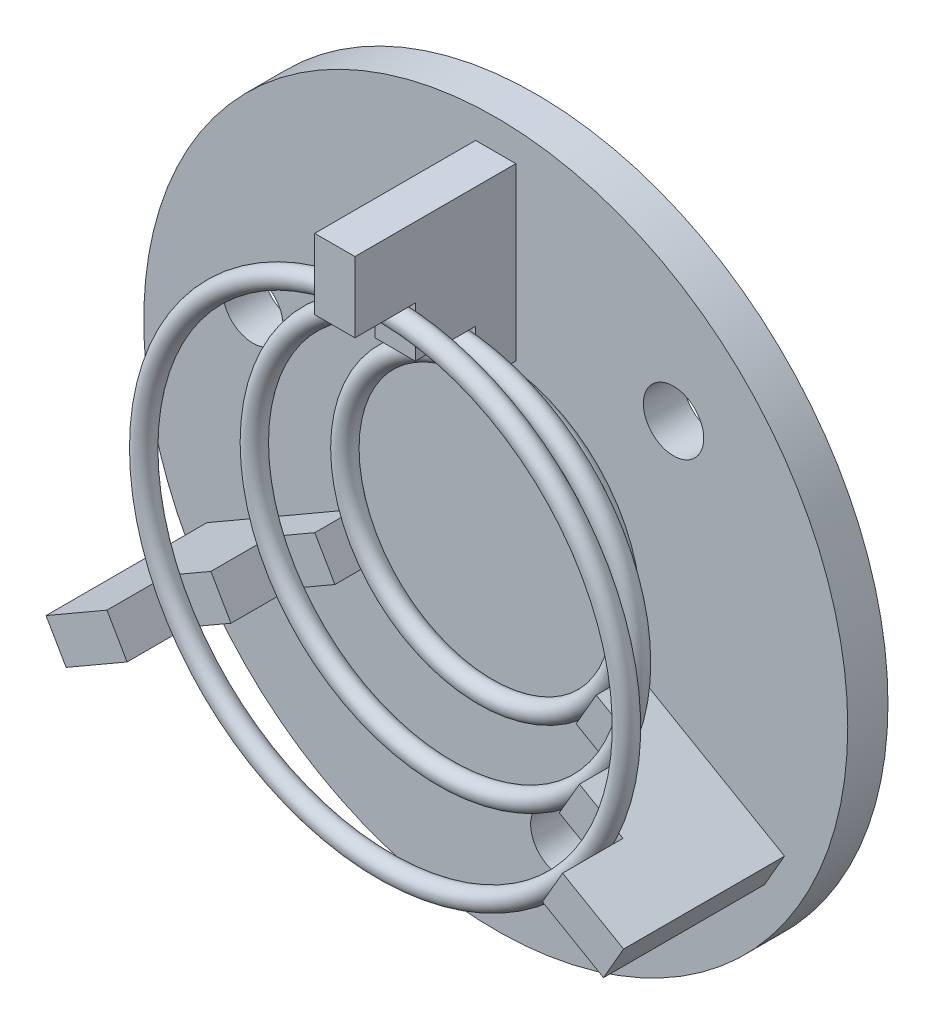
SolidWorks part; units mm, degrees
ref_plane "前视基准面" through (0, 0, 0) normal (0, 0, 1) x (1, 0, 0)
ref_plane "上视基准面" through (0, 0, 0) normal (0, 1, 0) x (1, 0, 0)
ref_plane "右视基准面" through (0, 0, 0) normal (1, 0, 0) x (0, 0, -1)
sketch "草图1" plane through (0, 0, 0) normal (0, 0, 1) x (1, 0, 0)
  circle A0 centre (0, 0) radius 17.5
  dimension "D1" = 35
extrude "凸台-拉伸1" add sketch "草图1" along normal blind 2
sketch "草图2" plane through (0, 0, 0) normal (0, 0, 1) x (1, 0, 0)
  line L0 (0, 0) -> (0, 13.5351)
  line L1 (0, 7.5) -> (1, 7.5)
  line L2 (0, 7.5) -> (-1, 7.5)
  line L3 (-1, 7.5) -> (-1, 16)
  line L4 (1, 7.5) -> (1, 16)
  line L5 (1, 16) -> (-1, 16)
  dimension "D1" = 1
  dimension "D2" = 1
  dimension "D3" = 8.5
  dimension "D4" = 13.5351
extrude "凸台-拉伸2" add sketch "草图2" along normal blind 10 contours L3 L5 L4 L1 L2
ref_plane "基准面1" through (0, 0, 10) normal (0, 0, 1) x (1, 0, 0)
sketch "草图3" plane through (0, 0, 10) normal (0, 0, 1) x (1, 0, 0)
  line L0 (1, 16) -> (-1, 16) construction
  line L1 (-1, 7.5) -> (-1, 16) construction
  line L2 (1, 7.5) -> (-1, 7.5) construction
  line L3 (1, 7.5) -> (1, 16) construction
  line L4 (1, 16) -> (-1, 16)
  line L5 (-1, 7.5) -> (-1, 16)
  line L6 (1, 7.5) -> (-1, 7.5)
  line L7 (1, 7.5) -> (1, 16)
  line L8 (-1, 7.5) -> (-1, 8.75)
  line L9 (-1, 7.5) -> (-1, 10)
  line L10 (-1, 10) -> (1, 10)
  line L11 (1, 10) -> (1, 7.5)
  line L12 (1, 10) -> (1, 7.5)
  line L13 (-1, 10) -> (1, 10)
  dimension "D1" = 2.5
extrude "切除-拉伸10" cut sketch "草图3" against normal blind 6 contours L10 L5 L6 L7 region at (0, 8.75, 10)
sketch "草图16" plane through (0, 0, 10) normal (0, 0, 1) x (1, 0, 0)
  line L0 (1, 10) -> (1, 16) construction
  line L1 (-1, 10) -> (1, 10) construction
  line L2 (-1, 10) -> (-1, 16) construction
  line L3 (1, 10) -> (1, 16)
  line L4 (-1, 10) -> (1, 10)
  line L5 (-1, 10) -> (-1, 16)
  line L6 (-1, 10) -> (-1, 12.5)
  line L7 (-1, 12.5) -> (1, 12.5)
  line L8 (1, 12.5) -> (1, 10)
  dimension "D1" = 2.5
extrude "切除-拉伸12" cut sketch "草图16" against normal blind 3 contours L7 L5 L4 L3 region at (0, 11.25, 10)
ref_plane "基准面8" through (0, 0, 2.5) normal (0, 0, 1) x (1, 0, 0)
sketch "草图17" plane through (0, 0, 2.5) normal (0, 0, 1) x (1, 0, 0)
  circle A0 centre (0, 0) radius 7
  dimension "D1" = 14
sketch "草图18" plane through (0, 0, 0) normal (0, 1, 0) x (1, 0, 0)
  line L0 (-7, -2.5) -> (7, -2.5) construction
  line L1 (-7, -2.5) -> (7, -2.5)
  circle A0 centre (-7, -2.5) radius 0.5
sweep "扫描3" add profiles "草图18" path "草图17"
ref_plane "基准面9" through (0, 0, 4.5) normal (0, 0, 1) x (1, 0, 0)
sketch "草图19" plane through (0, 0, 4.5) normal (0, 0, 1) x (1, 0, 0)
  circle A0 centre (0, 0) radius 9.5
  dimension "D1" = 19
sketch "草图20" plane through (0, 0, 0) normal (0, 1, 0) x (1, 0, 0)
  line L0 (-9.5, -4.5) -> (9.5, -4.5) construction
  line L1 (-9.5, -4.5) -> (9.5, -4.5)
  circle A0 centre (-9.5, -4.5) radius 0.5
  dimension "D1" = 1
sweep "扫描4" add profiles "草图20" path "草图19"
ref_plane "基准面10" through (0, 0, 7.5) normal (0, 0, 1) x (1, 0, 0)
sketch "草图21" plane through (0, 0, 7.5) normal (0, 0, 1) x (1, 0, 0)
  circle A0 centre (0, 0) radius 12
  dimension "D1" = 24
sketch "草图22" plane through (0, 0, 0) normal (0, 1, 0) x (1, 0, 0)
  line L0 (-12, -7.5) -> (12, -7.5) construction
  line L1 (-12, -7.5) -> (12, -7.5)
  circle A0 centre (-12, -7.5) radius 0.5
  dimension "D1" = 1
sweep "扫描5" add profiles "草图22" path "草图21"
ref_axis "基准轴3" through (0, 0, 2) along (0, 0, -1)
pattern_circular "阵列(圆周)7" count 3 over 360 about axis through (0, 0, 2) along (0, 0, -1) of "凸台-拉伸2", "切除-拉伸10", "切除-拉伸12"
sketch "草图23" plane through (0, 0, 0) normal (0, 0, 1) x (1, 0, 0)
  line L0 (-10.3253, -7.116) -> (-11.3253, -5.384) construction
  line L1 (-11.3253, -5.384) -> (-14.3564, -7.134) construction
  line L2 (-14.3564, -7.134) -> (-13.3564, -8.866) construction
  line L3 (-13.3564, -8.866) -> (-10.3253, -7.116) construction
  line L4 (-10.3253, -7.116) -> (-11.3253, -5.384)
  line L5 (-11.3253, -5.384) -> (-14.3564, -7.134)
  line L6 (-14.3564, -7.134) -> (-13.3564, -8.866)
  line L7 (-13.3564, -8.866) -> (-10.3253, -7.116)
  line L13 (12.3744, -12.3744) -> (-12.3744, 12.3744) construction
  line L16 (0, 0) -> (-12.3744, -12.3744) construction
  circle A0 centre (0, 0) radius 17.5 construction
  circle A1 centre (0, 0) radius 17.5
  circle A2 centre (8.8388, 8.8388) radius 1.5
  circle A3 centre (3.2352, -12.0741) radius 1.5
  circle A4 centre (-12.0741, 3.2352) radius 1.5
  point P21 (0, 0)
  dimension "D4" = 3
  dimension "D3" = 12.5
  dimension "D5" = 3
sketch "草图24" plane through (0, 0, 4.5) normal (0, 0, 1) x (1, 0, 0)
  circle A0 centre (3.2352, -12.0741) radius 1.5 construction
  circle A1 centre (8.8388, 8.8388) radius 1.5 construction
  circle A2 centre (-12.0741, 3.2352) radius 1.5 construction
  circle A3 centre (3.2352, -12.0741) radius 1.5
  circle A4 centre (8.8388, 8.8388) radius 1.5
  circle A5 centre (-12.0741, 3.2352) radius 1.5
extrude "切除-拉伸16" cut sketch "草图24" against normal blind 5
